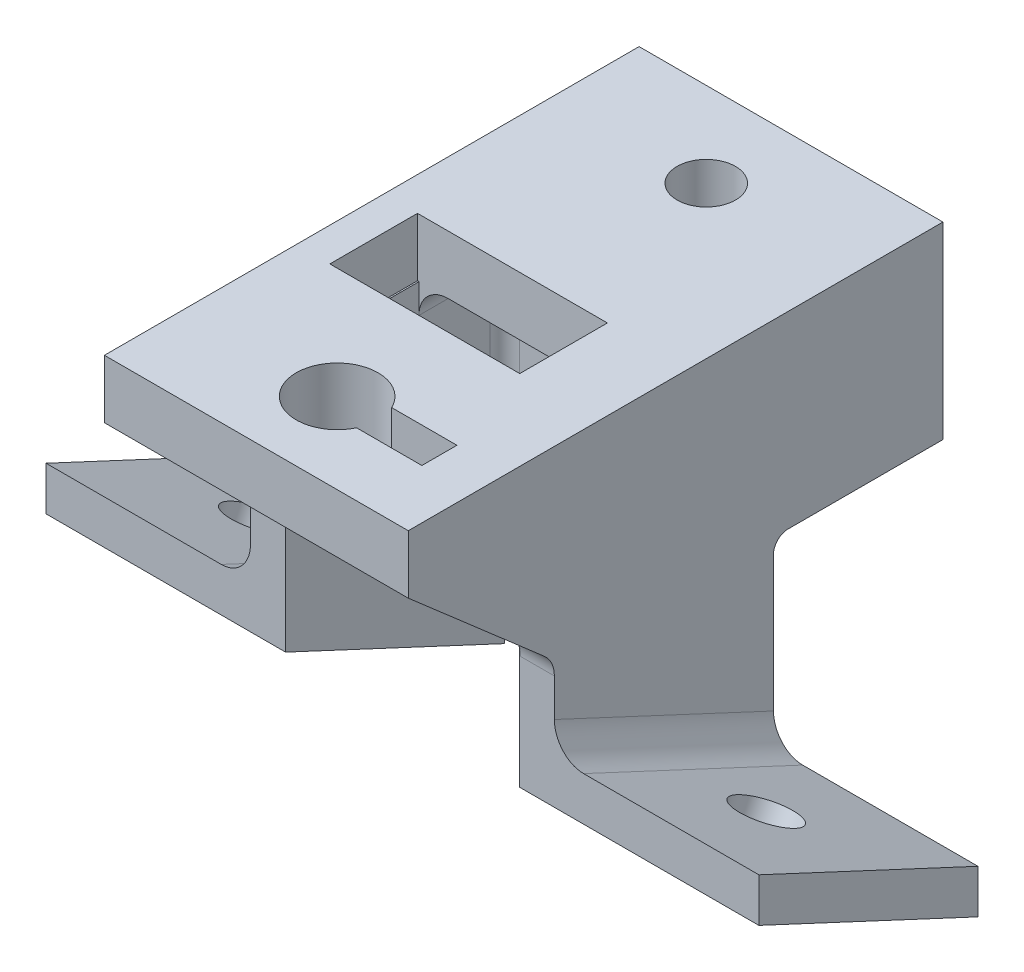
SolidWorks part; units mm, degrees
ref_plane "Front Plane" through (0, 0, 0) normal (0, 0, 1) x (1, 0, 0)
ref_plane "Top Plane" through (0, 0, 0) normal (0, 1, 0) x (1, 0, 0)
ref_plane "Right Plane" through (0, 0, 0) normal (1, 0, 0) x (0, 0, -1)
sketch "Sketch1" plane through (0, 0, 0) normal (0, 1, 0) x (1, 0, 0)
  line L1 (2.032, 2.1971) -> (2.032, -0.8509)
  line L6 (-11.176, -6.35) -> (15.24, -6.35)
  line L7 (-11.176, -6.35) -> (-11.176, 25.4)
  line L8 (-11.176, 25.4) -> (15.24, 25.4)
  line L9 (15.24, -6.35) -> (15.24, 25.4)
  line L15 (2.032, 2.1971) -> (10.922, 2.1971)
  line L16 (2.032, 2.1971) -> (2.032, -0.8509)
  line L17 (2.032, -0.8509) -> (10.922, -0.8509)
  line L18 (10.922, 2.1971) -> (10.922, -0.8509)
  circle A1 centre (2.032, 0.6731) radius 3.556
  point P6 (0, 0)
  point P13 (2.032, 0.6731)
  dimension "D1" = 7.112
  dimension "D2" = 8.89
  dimension "D3" = 13.208
  dimension "D4" = 7.0231
  dimension "D5" = 3.048
  dimension "D8" = 26.416
extrude "Boss-Extrude1" add sketch "Sketch1" along normal blind 5.08 contours L6 L9 L8 L7 A1 L18 L17 region at (1.9012, 0, -10.1623)
sketch "Sketch2" plane through (0, 5.08, 0) normal (0, 1, 0) x (1, 0, 0)
  line L1 (-8.255, 17.9451) -> (8.255, 17.9451)
  line L2 (-8.255, 17.9451) -> (-8.255, 10.3251)
  line L3 (-8.255, 10.3251) -> (8.255, 10.3251)
  line L4 (8.255, 17.9451) -> (8.255, 10.3251)
  line L5 (-11.176, -6.35) -> (-11.176, 25.4) construction
  arc A0 (5.2449, 2.1971) -> (5.2449, -0.8509) centre (2.032, 0.6731) ccw construction
  dimension "D4" = 7.62
  dimension "D1" = 16.51
  dimension "D2" = 2.921
  dimension "D3" = 9.652
extrude "Cut-Extrude1" cut sketch "Sketch2" against normal blind 5.08
sketch "Sketch3" plane through (-11.176, 0, 0) normal (-1, 0, 0) x (0, 0, 1)
  line L1 (-25.4, -22.098) -> (-25.4, -30.9812)
  line L4 (-25.4, -30.9812) -> (-6.35, -22.098)
  line L5 (-25.4, 0) -> (-6.35, 0)
  line L6 (-25.4, 0) -> (-25.4, -22.098)
  line L7 (-25.4, -22.098) -> (-6.35, -22.098)
  line L8 (-6.35, 0) -> (-6.35, -22.098)
  line M2 (-25.4, 0) -> (6.35, 0)
  dimension "D1" = 19.05
  dimension "D2" = 25
  dimension "D3" = 22.098
extrude "Boss-Extrude2" add sketch "Sketch3" against normal blind 26.416 contours L8 L6 L7 M2 | L7 L1 L4 region at (-11.176, -25.0591, -19.05) region at (-11.176, -11.049, -15.875)
sketch "Sketch6" plane through (-11.176, 0, 0) normal (-1, 0, 0) x (0, 0, 1)
  line L0 (6.35, 0) -> (-6.35, -11.049)
  line L1 (-6.35, 0) -> (-6.35, -22.098) construction
  line L2 (-6.35, -11.049) -> (-6.35, 0)
  line L3 (-6.35, 0) -> (6.35, 0)
extrude "Boss-Extrude3" add sketch "Sketch6" against normal blind 2.921
sketch "Sketch7" plane through (15.24, 0, 0) normal (1, 0, 0) x (0, 0, -1)
  line L0 (-6.35, 0) -> (6.35, -11.049)
  line L1 (6.35, 0) -> (6.35, -22.098) construction
  line L2 (6.35, -11.049) -> (6.35, 0)
  line L3 (6.35, 0) -> (-6.35, 0)
extrude "Boss-Extrude4" add sketch "Sketch7" against normal blind 2.921
sketch "Sketch8" plane through (15.24, 0, 0) normal (1, 0, 0) x (0, 0, -1)
  line L0 (6.35, -22.098) -> (25.4, -30.9812)
  line L1 (25.4, -30.9812) -> (25.4, -27.1712)
  line L2 (25.4, 5.08) -> (25.4, -30.9812) construction
  line L3 (25.4, -27.1712) -> (6.35, -18.288)
  line L4 (6.35, -11.049) -> (6.35, -22.098) construction
  line L5 (6.35, -18.288) -> (6.35, -22.098)
  dimension "D1" = 3.81
extrude "Boss-Extrude5" add sketch "Sketch8" along normal blind 17.78
sketch "Sketch9" plane through (-11.176, 0, 0) normal (-1, 0, 0) x (0, 0, 1)
  line L0 (-6.35, -22.098) -> (-25.4, -30.9812)
  line L1 (-25.4, -30.9812) -> (-25.4, -27.1712)
  line L2 (-25.4, 5.08) -> (-25.4, -30.9812) construction
  line L3 (-25.4, -27.1712) -> (-6.35, -18.288)
  line L4 (-6.35, -11.049) -> (-6.35, -22.098) construction
  line L5 (-6.35, -18.288) -> (-6.35, -22.098)
  dimension "D1" = 3.81
extrude "Boss-Extrude6" add sketch "Sketch9" along normal blind 17.78
sketch "Sketch10" plane through (0, -12.5895, 5.8706) normal (0, 0.9063, -0.4226) x (1, 0, 0)
  line L0 (-28.956, 13.4839) -> (-28.956, 34.5032) construction
  line L1 (33.02, 34.5032) -> (33.02, 13.4839) construction
  line L2 (33.02, 13.4839) -> (15.24, 13.4839) construction
  line L3 (-28.956, 13.4839) -> (-11.176, 13.4839) construction
  circle A0 centre (24.13, 23.9935) radius 2.54
  circle A1 centre (-20.066, 23.9935) radius 2.54
  dimension "D1" = 8.89
  dimension "D2" = 8.89
  dimension "D3" = 10.5096
  dimension "D4" = 10.5096
extrude "Cut-Extrude3" cut sketch "Sketch10" against normal blind 17.78
sketch "Sketch11" plane through (0, 0, -25.4) normal (0, 0, -1) x (-1, 0, 0)
  line L0 (-15.24, 5.08) -> (-15.24, -27.1712) construction
  line L1 (-12.192, 0) -> (8.128, 0)
  line L2 (-12.192, 0) -> (-12.192, -30.9812)
  line L3 (-12.192, -30.9812) -> (8.128, -30.9812)
  line L4 (8.128, 0) -> (8.128, -30.9812)
  line L5 (11.176, 5.08) -> (-15.24, 5.08) construction
  line L6 (-33.02, -30.9812) -> (28.956, -30.9812) construction
  dimension "D1" = 20.32
  dimension "D2" = 3.048
  dimension "D3" = 5.08
  dimension "D4" = 0
extrude "Cut-Extrude4" cut sketch "Sketch11" against normal blind 22.86
fillet "Fillet3" radius 2.54 5 edges at (-8.128, 0, -8.3375) (-8.128, 0, -21.6725) (12.192, 0, -15.875) (15.24, -22.7296, -15.875) (-11.176, -22.7296, -15.875)
fillet "Fillet4" radius 2.54 2 edges at (-9.7155, -11.049, -6.35) (13.7795, -11.049, -6.35)
sketch "Sketch12" plane through (0, 5.08, 0) normal (0, 1, 0) x (1, 0, 0)
  line L1 (-11.176, 25.4) -> (15.24, 25.4)
  line L2 (-11.176, 25.4) -> (-11.176, 40.132)
  line L3 (-11.176, 40.132) -> (15.24, 40.132)
  line L4 (15.24, 25.4) -> (15.24, 40.132)
  circle A0 centre (2.032, 32.766) radius 2.54
  dimension "D5" = 5.08
  dimension "D1" = 26.416
  dimension "D2" = 14.732
  dimension "D3" = 13.208
  dimension "D4" = 7.366
extrude "Boss-Extrude7" add sketch "Sketch12" against normal blind 16.383
fillet "Fillet5" radius 1.27 5 edges at (-8.128, -6.9215, -25.4) (-7.3841, -0.7439, -25.4) (2.032, 0, -25.4) (11.4481, -0.7439, -25.4) (12.192, -6.9215, -25.4)
fillet "Fillet6" radius 1.27 2 edges at (-9.652, -11.303, -25.4) (13.716, -11.303, -25.4)
